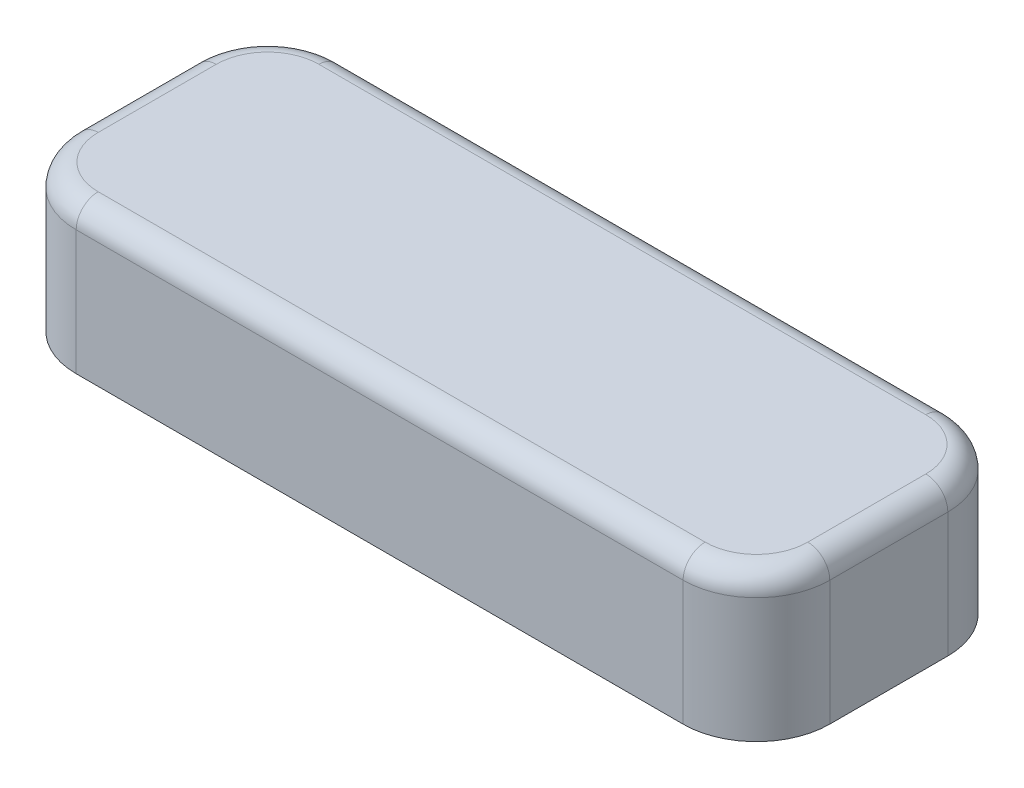
SolidWorks part; units mm, degrees
ref_plane "前视基准面" through (0, 0, 0) normal (0, 0, 1) x (1, 0, 0)
ref_plane "上视基准面" through (0, 0, 0) normal (0, 1, 0) x (1, 0, 0)
ref_plane "右视基准面" through (0, 0, 0) normal (1, 0, 0) x (0, 0, -1)
other "Configuration Table"
sketch "草图1" plane through (0, 0, 0) normal (0, 1, 0) x (1, 0, 0)
  line L0 (-2.2, 0) -> (2.2, 0) construction
  line L1 (0, 2.2) -> (0, -2.2) construction
  line L2 (2.2, 0.6) -> (2.2, -0.6)
  line L3 (-0.6, 2.2) -> (0.6, 2.2)
  line L4 (-2.2, -0.6) -> (-2.2, 0.6)
  line L5 (-0.6, -2.2) -> (0.6, -2.2)
  line L6 (-0.6, 2.2) -> (-0.6, 0.6)
  line L7 (-0.6, 0.6) -> (-2.2, 0.6)
  line L8 (-2.2, -0.6) -> (-0.6, -0.6)
  line L9 (-0.6, -0.6) -> (-0.6, -2.2)
  line L10 (0.6, -2.2) -> (0.6, -0.6)
  line L11 (0.6, -0.6) -> (2.2, -0.6)
  line L12 (2.2, 0.6) -> (0.6, 0.6)
  line L13 (0.6, 0.6) -> (0.6, 2.2)
  line L14 (-11.9062, 0) -> (11.9062, 0) construction
  line L15 (-14.1063, 0) -> (-9.7062, 0) construction
  line L16 (-11.9062, 2.2) -> (-11.9062, -2.2) construction
  line L17 (-14.1063, -0.6) -> (-14.1063, 0.6)
  line L18 (-12.5062, -2.2) -> (-11.3063, -2.2)
  line L19 (-11.3063, 2.2) -> (-12.5062, 2.2)
  line L20 (-9.7062, -0.6) -> (-9.7062, 0.6)
  line L21 (-14.1063, -0.6) -> (-12.5062, -0.6)
  line L22 (-12.5062, -0.6) -> (-12.5062, -2.2)
  line L23 (-11.3063, -2.2) -> (-11.3063, -0.6)
  line L24 (-11.3063, -0.6) -> (-9.7062, -0.6)
  line L25 (-9.7062, 0.6) -> (-11.3063, 0.6)
  line L26 (-11.3063, 0.6) -> (-11.3063, 2.2)
  line L27 (-12.5062, 2.2) -> (-12.5062, 0.6)
  line L28 (-12.5062, 0.6) -> (-14.1063, 0.6)
  line L29 (9.7062, 0) -> (14.1063, 0) construction
  line L30 (11.9062, -2.2) -> (11.9062, 2.2) construction
  line L31 (9.7062, 0.6) -> (9.7062, -0.6)
  line L32 (11.3063, 2.2) -> (12.5062, 2.2)
  line L33 (14.1063, -0.6) -> (14.1063, 0.6)
  line L34 (11.3063, -2.2) -> (12.5062, -2.2)
  line L35 (9.7062, 0.6) -> (11.3063, 0.6)
  line L36 (11.3063, 0.6) -> (11.3063, 2.2)
  line L37 (12.5062, 2.2) -> (12.5062, 0.6)
  line L38 (12.5062, 0.6) -> (14.1063, 0.6)
  line L39 (14.1063, -0.6) -> (12.5062, -0.6)
  line L40 (12.5062, -0.6) -> (12.5062, -2.2)
  line L41 (11.3063, -2.2) -> (11.3063, -0.6)
  line L42 (11.3063, -0.6) -> (9.7062, -0.6)
  circle A0 centre (0, 0) radius 2.8
  circle A1 centre (-11.9062, 0) radius 2.8
  circle A2 centre (11.9062, 0) radius 2.8
  point P4 (0, 0)
  point P7 (0, 0)
  point P10 (2.2, 0)
  point P13 (0, 2.2)
  point P16 (-2.2, 0)
  point P19 (0, -2.2)
  point P28 (0, 0)
  point P31 (-11.9062, 0)
  point P34 (-11.9062, 0)
  point P37 (-14.1063, 0)
  point P40 (-11.9062, -2.2)
  point P43 (-11.9062, 2.2)
  point P46 (-9.7062, 0)
  point P54 (11.9062, 0)
  point P57 (11.9062, 0)
  point P60 (9.7062, 0)
  point P63 (11.9062, 2.2)
  point P66 (14.1063, 0)
  point P69 (11.9062, -2.2)
  dimension "D7" = 5.6
  dimension "D15" = 5.6
  dimension "D22" = 5.6
  dimension "D1" = 4.4
  dimension "D2" = 4.4
  dimension "D3" = 1.2
  dimension "D4" = 1.2
  dimension "D5" = 1.2
  dimension "D6" = 1.2
  dimension "D8" = 23.8125
  dimension "D9" = 4.4
  dimension "D10" = 4.4
  dimension "D11" = 1.2
  dimension "D12" = 1.2
  dimension "D13" = 1.2
  dimension "D14" = 1.2
  dimension "D16" = 4.4
  dimension "D17" = 4.4
  dimension "D18" = 1.2
  dimension "D19" = 1.2
  dimension "D20" = 1.2
  dimension "D21" = 1.2
extrude "凸台-拉伸1" add sketch "草图1" against normal blind 8
sketch "草图2" plane through (0, 0, 0) normal (0, 1, 0) x (1, 0, 0)
  line L0 (0, -9.025) -> (0, 9.025) construction
  line L1 (-25.6938, 9.025) -> (25.6938, 9.025)
  line L2 (-25.6938, -9.025) -> (25.6938, -9.025)
  line L3 (-25.6938, 9.025) -> (-25.6938, -9.025)
  line L4 (25.6938, 9.025) -> (25.6938, -9.025)
  point P4 (0, 0)
  point P8 (0, 9.025)
  point P11 (0, -9.025)
  dimension "D1" = 18.05
  dimension "D2" = 51.3875
extrude "凸台-拉伸2" add sketch "草图2" along normal blind 1
sketch "草图3" plane through (0, 0, 0) normal (0, 1, 0) x (1, 0, 0)
  line L4 (25.6938, -9.025) -> (25.6938, 9.025)
  line L5 (-25.6938, -9.025) -> (25.6938, -9.025)
  line L6 (-25.6938, 9.025) -> (-25.6938, -9.025)
  line L7 (25.6938, 9.025) -> (-25.6938, 9.025)
  line L8 (25.6938, -9.025) -> (25.6938, 9.025)
  line L9 (-25.6938, -9.025) -> (25.6938, -9.025)
  line L10 (-25.6938, 9.025) -> (-25.6938, -9.025)
  line L11 (25.6938, 9.025) -> (-25.6938, 9.025)
  line L20 (24.6938, -8.025) -> (24.6938, 8.025)
  line L21 (24.6938, 8.025) -> (-24.6938, 8.025)
  line L22 (-24.6938, 8.025) -> (-24.6938, -8.025)
  line L23 (-24.6938, -8.025) -> (24.6938, -8.025)
  line L24 (24.6938, -8.025) -> (24.6938, 8.025)
  line L25 (24.6938, 8.025) -> (-24.6938, 8.025)
  line L26 (-24.6938, 8.025) -> (-24.6938, -8.025)
  line L27 (-24.6938, -8.025) -> (24.6938, -8.025)
  dimension "D1" = 0
  dimension "D2" = 1
extrude "凸台-拉伸3" add sketch "草图3" against normal blind 9
sketch "草图4" plane through (0, 0, 0) normal (0, 1, 0) x (1, 0, 0)
  line L0 (9.7062, 0.6) -> (9.7062, -0.6) construction
  line L1 (12.5062, 2.2) -> (11.3063, 2.2) construction
  line L2 (11.3063, -2.2) -> (12.5062, -2.2) construction
  line L3 (14.1063, -0.6) -> (14.1063, 0.6) construction
  line L4 (2.2, -0.6) -> (2.2, 0.6) construction
  line L5 (0.6, 2.2) -> (-0.6, 2.2) construction
  line L6 (-2.2, 0.6) -> (-2.2, -0.6) construction
  line L7 (-0.6, -2.2) -> (0.6, -2.2) construction
  line L8 (-11.3063, 2.2) -> (-12.5062, 2.2) construction
  line L9 (-9.7062, -0.6) -> (-9.7062, 0.6) construction
  line L10 (-12.5062, -2.2) -> (-11.3063, -2.2) construction
  line L11 (-14.1063, 0.6) -> (-14.1063, -0.6) construction
  line L12 (9.7062, 0.6) -> (9.7062, -0.6)
  line L13 (12.5062, 2.2) -> (11.3063, 2.2)
  line L14 (11.3063, -2.2) -> (12.5062, -2.2)
  line L15 (14.1063, -0.6) -> (14.1063, 0.6)
  line L16 (2.2, -0.6) -> (2.2, 0.6)
  line L17 (0.6, 2.2) -> (-0.6, 2.2)
  line L18 (-2.2, 0.6) -> (-2.2, -0.6)
  line L19 (-0.6, -2.2) -> (0.6, -2.2)
  line L20 (-11.3063, 2.2) -> (-12.5062, 2.2)
  line L21 (-9.7062, -0.6) -> (-9.7062, 0.6)
  line L22 (-12.5062, -2.2) -> (-11.3063, -2.2)
  line L23 (-14.1063, 0.6) -> (-14.1063, -0.6)
  line L24 (-14.1063, -0.6) -> (-24.6938, -0.6)
  line L25 (-24.6938, 8.025) -> (-24.6938, -8.025) construction
  line L26 (-24.6938, -0.6) -> (-24.6938, 0.6)
  line L27 (-24.6938, 8.025) -> (-24.6938, -8.025) construction
  line L28 (-24.6938, 0.6) -> (-14.1063, 0.6)
  line L29 (-12.5062, -2.2) -> (-12.5062, -8.025)
  line L30 (-24.6938, -8.025) -> (24.6938, -8.025) construction
  line L31 (-12.5062, -8.025) -> (-11.3063, -8.025)
  line L32 (-24.6938, -8.025) -> (24.6938, -8.025) construction
  line L33 (-11.3063, -8.025) -> (-11.3063, -2.2)
  line L34 (-12.5062, 2.2) -> (-12.5062, 8.025)
  line L35 (24.6938, 8.025) -> (-24.6938, 8.025) construction
  line L36 (-12.5062, 8.025) -> (-11.3063, 8.025)
  line L37 (24.6938, 8.025) -> (-24.6938, 8.025) construction
  line L38 (-11.3063, 8.025) -> (-11.3063, 2.2)
  line L39 (-9.7062, -0.6) -> (-2.2, -0.6)
  line L40 (-2.2, 0.6) -> (-9.7062, 0.6)
  line L41 (-0.6, -2.2) -> (-0.6, -8.025)
  line L42 (-0.6, -8.025) -> (0.6, -8.025)
  line L43 (0.6, -8.025) -> (0.6, -2.2)
  line L44 (2.2, -0.6) -> (9.7062, -0.6)
  line L45 (9.7062, 0.6) -> (2.2, 0.6)
  line L46 (0.6, 2.2) -> (0.6, 8.025)
  line L47 (0.6, 8.025) -> (-0.6, 8.025)
  line L48 (-0.6, 8.025) -> (-0.6, 2.2)
  line L49 (11.3063, -2.2) -> (11.3063, -8.025)
  line L50 (11.3063, -8.025) -> (12.5062, -8.025)
  line L51 (12.5062, -8.025) -> (12.5062, -2.2)
  line L52 (14.1063, -0.6) -> (24.6938, -0.6)
  line L53 (24.6938, -8.025) -> (24.6938, 8.025) construction
  line L54 (24.6938, -0.6) -> (24.6938, 0.6)
  line L55 (24.6938, 0.6) -> (14.1063, 0.6)
  line L56 (12.5062, 2.2) -> (12.5062, 8.025)
  line L57 (12.5062, 8.025) -> (11.3062, 8.025)
  line L58 (11.3062, 8.025) -> (11.3063, 2.2)
extrude "凸台-拉伸4" add sketch "草图4" against normal blind 2.5
fillet "圆角1" radius 5 8 edges at (-25.6938, -4, -9.025) (25.6938, -4, -9.025) (25.6938, -4, 9.025) (-25.6938, -4, 9.025) (-24.6938, -4.5, -8.025) (24.6938, -4.5, -8.025) (24.6938, -4.5, 8.025) (-24.6938, -4.5, 8.025)
fillet "圆角2" radius 1.5 24 edges at (24.6938, 0, 1.8125) (16.1, 0, 8.025) (16.1, 0, -8.025) (24.6938, 0, -1.8125) (-24.6938, 0, -1.8125) (-16.1, 0, -8.025) (-16.1, 0, 8.025) (-24.6938, 0, 1.8125) (24.2293, 1, -7.5605) (25.6938, 1, 0) (24.2293, 1, 7.5605) (0, 1, 9.025) (-24.2293, 1, 7.5605) (-25.6938, 1, 0) (-24.2293, 1, -7.5605) (0, 1, -9.025) (5.9531, 0, -8.025) (-5.9531, 0, -8.025) (-5.9531, 0, 8.025) (5.9531, 0, 8.025) (23.2293, 0, 6.5605) (23.2293, 0, -6.5605) (-23.2293, 0, -6.5605) (-23.2293, 0, 6.5605)
